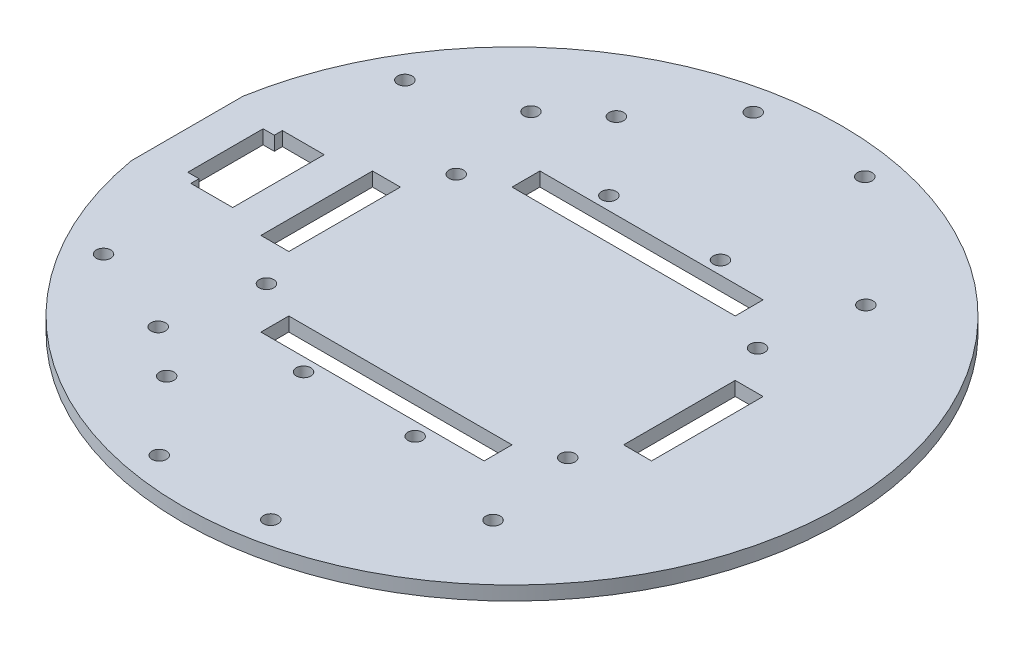
SolidWorks part; units mm, degrees
material "Acrylic (Medium-high impact)"
ref_plane "Front Plane" through (0, 0, 0) normal (0, 0, 1) x (1, 0, 0)
ref_plane "Top Plane" through (0, 0, 0) normal (0, 1, 0) x (1, 0, 0)
ref_plane "Right Plane" through (0, 0, 0) normal (1, 0, 0) x (0, 0, -1)
sketch "Sketch1" plane through (0, 0, 0) normal (0, 1, 0) x (1, 0, 0)
  line L0 (-73.9169, 12.7) -> (-73.9169, -12.7)
  line L1 (-73.9169, 12.7) -> (-73.9169, -12.7) construction
  line L2 (-34.29, 21.59) -> (34.29, 21.59) construction
  line L3 (34.29, 21.59) -> (34.29, -21.59) construction
  line L4 (34.29, -21.59) -> (-34.29, -21.59) construction
  line L5 (-34.29, -21.59) -> (-34.29, 21.59) construction
  line L6 (0, 21.59) -> (0, 75) construction
  line L7 (34.29, 0) -> (75, 0) construction
  line L8 (0, -25.4) -> (0, -21.59) construction
  line L9 (-34.29, 0) -> (-38.1, 0) construction
  line L10 (-25.4, 31.75) -> (25.4, 31.75)
  line L11 (-25.4, 31.75) -> (-25.4, 25.4)
  line L12 (-25.4, 25.4) -> (25.4, 25.4)
  line L13 (25.4, 31.75) -> (25.4, 25.4)
  line L14 (38.1, 12.7) -> (44.45, 12.7)
  line L15 (38.1, 12.7) -> (38.1, -12.7)
  line L16 (38.1, -12.7) -> (44.45, -12.7)
  line L17 (44.45, 12.7) -> (44.45, -12.7)
  line L18 (25.4, -25.4) -> (-25.4, -25.4)
  line L19 (25.4, -25.4) -> (25.4, -31.75)
  line L20 (25.4, -31.75) -> (-25.4, -31.75)
  line L21 (-25.4, -25.4) -> (-25.4, -31.75)
  line L22 (-44.45, -12.7) -> (-38.1, -12.7)
  line L23 (-44.45, -12.7) -> (-44.45, 12.7)
  line L24 (-44.45, 12.7) -> (-38.1, 12.7)
  line L25 (-38.1, -12.7) -> (-38.1, 12.7)
  line L26 (38.1, 12.7) -> (34.29, 12.7) construction
  line L27 (25.4, 25.4) -> (25.4, 21.59) construction
  line L28 (-24.25, -37.9184) -> (24.25, -37.9184) construction
  line L29 (24.25, -37.9184) -> (24.25, -64.4184) construction
  line L30 (-12.7, -37.9184) -> (-12.7, -34.7434) construction
  line L31 (24.25, -64.4184) -> (-24.25, -64.4184) construction
  line L32 (-24.25, -64.4184) -> (-24.25, -37.9184) construction
  line L33 (-24.25, -64.4184) -> (-26.4232, -70.1913) construction
  line L34 (24.25, -64.4184) -> (26.4232, -70.1913) construction
  line L35 (-24.25, -37.9184) -> (-24.25, -31.75) construction
  line L36 (0, -37.9184) -> (0, -64.4184) construction
  line L37 (-53.151, 0) -> (-44.45, 0) construction
  line L38 (-27.425, -51.1684) -> (-24.25, -51.1684) construction
  line L39 (-12.7, -67.5934) -> (-12.7, -64.4184) construction
  line L40 (-65.216, 8.5725) -> (-62.676, 8.5725)
  line L41 (-65.216, 8.5725) -> (-65.216, -8.5725)
  line L42 (-65.216, -8.5725) -> (-62.676, -8.5725)
  line L43 (-53.151, 8.5725) -> (-53.151, -8.5725)
  line L44 (-62.676, 8.5725) -> (-62.676, 10.414)
  line L45 (-62.676, 10.414) -> (-53.151, 10.414)
  line L46 (-53.151, 10.414) -> (-53.151, 8.5725)
  line L47 (-62.676, -8.5725) -> (-62.676, -10.414)
  line L48 (-62.676, -10.414) -> (-53.151, -10.414)
  line L49 (-53.151, -10.414) -> (-53.151, -8.5725)
  line L50 (-65.216, 0) -> (-73.9169, 0) construction
  line L51 (55.1757, 50.8) -> (55.1757, -50.8) construction
  arc A0 (-73.9169, -12.7) -> (-73.9169, 12.7) centre (0, 0) ccw
  arc A1 (55.356, -50.6035) -> (55.356, 50.6035) centre (0, 0) ccw construction
  circle A2 centre (-34.29, 21.59) radius 1.651
  circle A3 centre (34.29, 21.59) radius 1.651
  circle A4 centre (-34.29, -21.59) radius 1.651
  circle A5 centre (34.29, -21.59) radius 1.651
  circle A6 centre (-39.6269, 47.4285) radius 1.651 construction
  circle A7 centre (38.1, -42.418) radius 1.651
  circle A8 centre (-38.1, -42.418) radius 1.651
  circle A9 centre (-58.6769, -34.29) radius 1.651
  circle A10 centre (-58.6769, 34.29) radius 1.651
  circle A11 centre (-38.1, 42.418) radius 1.651
  circle A12 centre (38.1, 42.418) radius 1.651
  circle A13 centre (51.7494, -47.4285) radius 1.651 construction
  circle A14 centre (12.7, -67.5934) radius 1.651
  circle A15 centre (12.7, -34.7434) radius 1.651
  circle A16 centre (12.7, 34.7434) radius 1.651
  circle A17 centre (12.7, 67.5934) radius 1.651
  circle A22 centre (-27.425, -51.1684) radius 1.651
  circle A23 centre (-12.7, -34.7434) radius 1.651
  circle A24 centre (-12.7, -67.5934) radius 1.651
  circle A25 centre (-12.7, 67.5934) radius 1.651
  circle A26 centre (-27.425, 51.1684) radius 1.651
  circle A27 centre (-12.7, 34.7434) radius 1.651
  dimension "D11" = 3.302
  dimension "D1" = 68.58
  dimension "D2" = 43.18
  dimension "D3" = 3.81
  dimension "D4" = 6.35
  dimension "D5" = 50.8
  dimension "D6" = 25.4
  dimension "D7" = 48.5
  dimension "D8" = 26.5
  dimension "D9" = 12.7
  dimension "D10" = 3.175
  dimension "D12" = 17.145
  dimension "D13" = 12.065
  dimension "D14" = 101.6
  dimension "D15" = 2.54
  dimension "D16" = 20.828
  dimension "D17" = 9.525
extrude "Boss-Extrude1" add sketch "Sketch1" along normal blind 3.175
